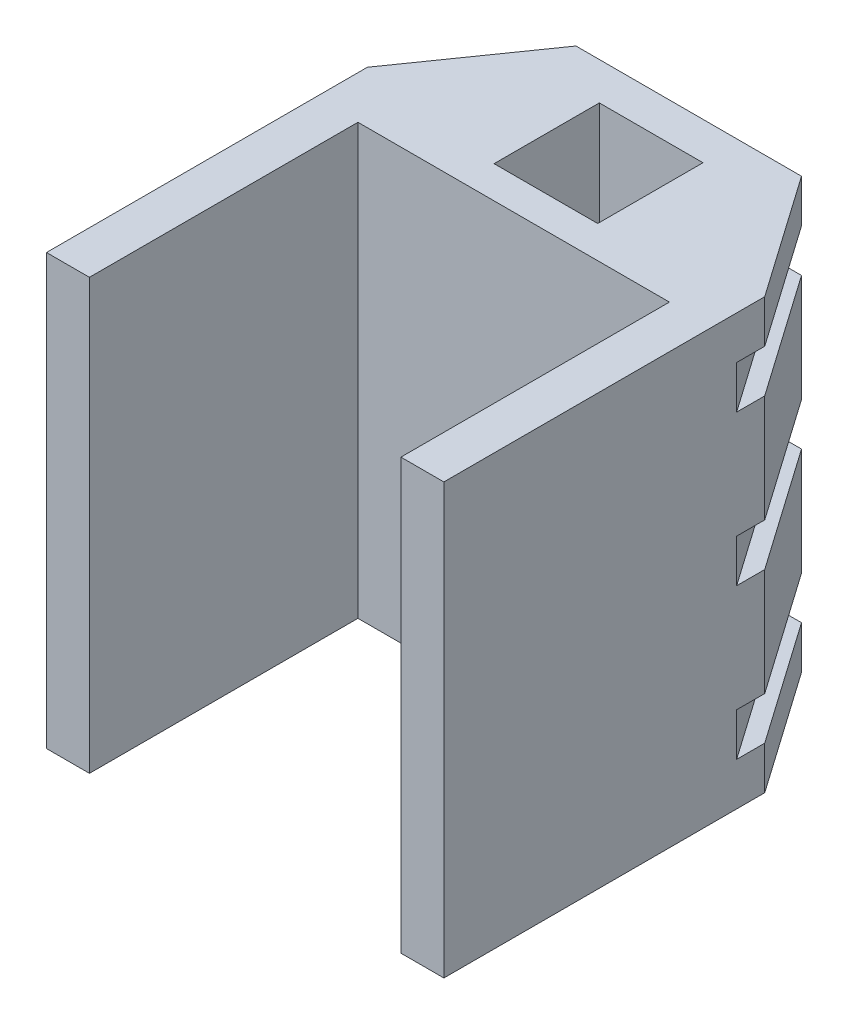
SolidWorks part; units mm, degrees
note: The reader was unsure of these and kept them because the rebuilt part matched: shared geometry of "Sketch2<3>", "Sketch2<5>", "Sketch2<4>".
ref_plane "Front Plane" through (0, 0, 0) normal (0, 0, 1) x (1, 0, 0)
ref_plane "Top Plane" through (0, 0, 0) normal (0, 1, 0) x (1, 0, 0)
ref_plane "Right Plane" through (0, 0, 0) normal (1, 0, 0) x (0, 0, -1)
sketch "Sketch2" plane through (0, 0, 0) normal (0, 0, 1) x (1, 0, 0)
  line L1 (4.825, -20) -> (-4.825, -20)
  line L2 (4.825, -20) -> (4.825, 20)
  line L3 (4.825, 20) -> (-4.825, 20)
  line L4 (-4.825, -20) -> (-4.825, 20)
  line L5 (4.825, -20) -> (-4.825, 20) construction
  line L6 (4.825, 20) -> (-4.825, -20) construction
  line L7 (14.5, -20) -> (-14.5, -20)
  line L8 (14.5, -20) -> (14.5, 20)
  line L9 (14.5, 20) -> (-14.5, 20)
  line L10 (-14.5, -20) -> (-14.5, 20)
  line L11 (14.5, -20) -> (-14.5, 20) construction
  line L12 (14.5, 20) -> (-14.5, -20) construction
  line L13 (18.5, -20) -> (-18.5, -20)
  line L14 (18.5, -20) -> (18.5, 20)
  line L15 (18.5, 20) -> (-18.5, 20)
  line L16 (-18.5, -20) -> (-18.5, 20)
  line L17 (18.5, -20) -> (-18.5, 20) construction
  line L18 (18.5, 20) -> (-18.5, -20) construction
  point P0 (0, 0)
  point P6 (0, 0)
  point P11 (0, 0)
  dimension "D1" = 9.65
  dimension "D2" = 29
  dimension "D3" = 37
  dimension "D4" = 40
extrude "BottomBase" add sketch "Sketch2" along normal blind 3.5 contours L16 L13 L10 L15 | L10 L7 L4 L9 | L4 L1 L2 L3 | L8 L9 L2 L7 | L14 L15 L8 L13
extrude "U" add sketch "Sketch2<3>" along normal blind 9.8 from surface at 3.5 contours L8 L9 L2 L7 | L14 L15 L8 L13 | L10 L7 L4 L9 | L16 L13 L10 L15 starting at face at (0, 0, 3.5)
sketch "Sketch2<3>" plane through (0, 0, 0) normal (0, 0, 1) x (1, 0, 0) same geometry as "Sketch2"
extrude "topForU" add sketch "Sketch2<5>" along normal blind 3 from vertex at 13.3 contours L14 L15 L16 L13
sketch "Sketch2<5>" plane through (0, 0, 0) normal (0, 0, 1) x (1, 0, 0) same geometry as "Sketch2"
chamfer "angledBottom" distance 8 angle 55 2 edges at (-18.5, 0, 0) (18.5, 0, 0)
extrude "sidesToHoldMotor" add sketch "Sketch2<4>" along normal blind 25 from vertex at 16.3 contours L16 L13 L10 L15 | L14 L15 L8 L13
sketch "Sketch2<4>" plane through (0, 0, 0) normal (0, 0, 1) x (1, 0, 0) same geometry as "Sketch2"
sketch "Sketch3" plane through (7.0456, 0, -4.9334) normal (0.8192, 0, -0.5736) x (-0.5736, 0, -0.8192)
  line L0 (-9.1062, -19.362) -> (-9.1062, 18.8867) construction
  line L1 (-25.9517, 2) -> (7.7393, 2)
  line L2 (-25.9517, 2) -> (-25.9517, -2)
  line L3 (-25.9517, -2) -> (7.7393, -2)
  line L4 (7.7393, 2) -> (7.7393, -2)
  line L5 (-25.9517, 2) -> (7.7393, -2) construction
  line L6 (-25.9517, -2) -> (7.7393, 2) construction
  line L8 (-25.9517, 16) -> (7.7393, 16)
  line L9 (-25.9517, 16) -> (-25.9517, 12)
  line L10 (-25.9517, 12) -> (7.7393, 12)
  line L11 (7.7393, 16) -> (7.7393, 12)
  line L12 (-25.9517, 16) -> (7.7393, 12) construction
  line L13 (-25.9517, 12) -> (7.7393, 16) construction
  line L14 (-25.9517, -12) -> (7.7393, -12)
  line L15 (-25.9517, -12) -> (-25.9517, -16)
  line L16 (-25.9517, -16) -> (7.7393, -16)
  line L17 (7.7393, -12) -> (7.7393, -16)
  line L18 (-25.9517, -12) -> (7.7393, -16) construction
  line L19 (-25.9517, -16) -> (7.7393, -12) construction
  point P0 (-9.1062, 0)
  point P8 (-9.1062, 14)
  point P13 (-9.1062, -14)
  dimension "D1" = 4
  dimension "D2" = 4
  dimension "D3" = 4
  dimension "D4" = 10
  dimension "D5" = 10
extrude "zipTieHole" cut sketch "Sketch3" against normal blind 1.5
sketch "Sketch4" plane through (-7.0456, 0, -4.9334) normal (-0.8192, 0, -0.5736) x (-0.5736, 0, 0.8192)
  line L1 (25.1723, -2) -> (-25.1723, -2)
  line L2 (25.1723, -2) -> (25.1723, 2)
  line L3 (25.1723, 2) -> (-25.1723, 2)
  line L4 (-25.1723, -2) -> (-25.1723, 2)
  line L5 (25.1723, -2) -> (-25.1723, 2) construction
  line L6 (25.1723, 2) -> (-25.1723, -2) construction
  line L7 (25.1723, 12) -> (-25.1723, 12)
  line L8 (25.1723, 12) -> (25.1723, 16)
  line L9 (25.1723, 16) -> (-25.1723, 16)
  line L10 (-25.1723, 12) -> (-25.1723, 16)
  line L11 (25.1723, 12) -> (-25.1723, 16) construction
  line L12 (25.1723, 16) -> (-25.1723, 12) construction
  line L13 (25.1723, -16) -> (-25.1723, -16)
  line L14 (25.1723, -16) -> (25.1723, -12)
  line L15 (25.1723, -12) -> (-25.1723, -12)
  line L16 (-25.1723, -16) -> (-25.1723, -12)
  line L17 (25.1723, -16) -> (-25.1723, -12) construction
  line L18 (25.1723, -12) -> (-25.1723, -16) construction
  point P0 (0, 0)
  point P6 (0, 14)
  point P11 (0, -14)
  dimension "D1" = 4
  dimension "D2" = 4
  dimension "D3" = 4
  dimension "D4" = 10
  dimension "D5" = 10
extrude "zipTieHole2" cut sketch "Sketch4" against normal blind 1.5
equation "\"D3@Sketch2\"=\"D2@Sketch2\"+8"
